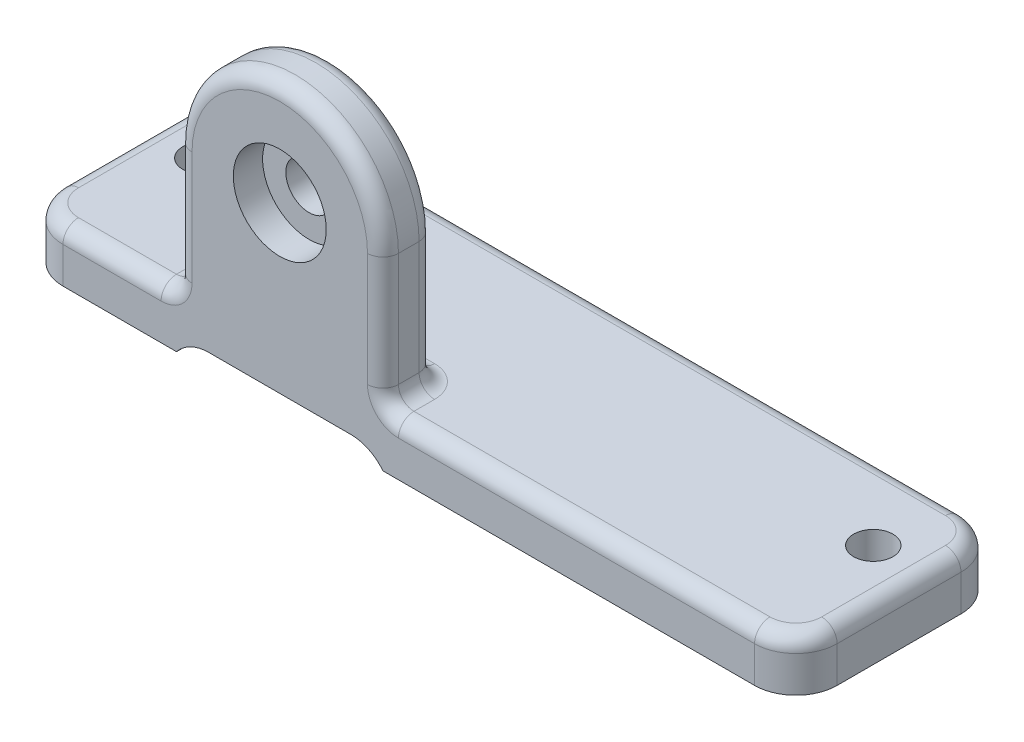
SolidWorks part; units mm, degrees
ref_plane "Front Plane" through (0, 0, 0) normal (0, 0, 1) x (1, 0, 0)
ref_plane "Top Plane" through (0, 0, 0) normal (0, 1, 0) x (1, 0, 0)
ref_plane "Right Plane" through (0, 0, 0) normal (1, 0, 0) x (0, 0, -1)
sketch "Croquis1" plane through (0, 0, 0) normal (0, 1, 0) x (1, 0, 0)
  line L1 (0, 0) -> (150, 0)
  line L2 (0, 0) -> (0, 40)
  line L3 (0, 40) -> (150, 40)
  line L4 (150, 0) -> (150, 40)
  dimension "D1" = 150
  dimension "D2" = 40
extrude "Saliente-Extruir1" add sketch "Croquis1" along normal blind 10 contours L2 L1 L4 L3
sketch "Croquis2" plane through (0, 0, 0) normal (0, 0, 1) x (1, 0, 0)
  line L0 (30, 0) -> (30, 35)
  line L1 (0, 0) -> (150, 0) construction
  line L2 (70, 35) -> (70, 0)
  line L3 (70, 0) -> (30, 0)
  line L4 (0, 10) -> (0, 0) construction
  arc A0 (30, 35) -> (70, 35) centre (50, 35) cw
  point P9 (0, 5)
  dimension "D3" = 20
  dimension "D1" = 50
  dimension "D2" = 35
extrude "Saliente-Extruir2" add sketch "Croquis2" against normal blind 10
sketch "Croquis3" plane through (0, 0, 0) normal (0, 0, 1) x (1, 0, 0)
  line L0 (0, 0) -> (150, 0) construction
  line L1 (30, 0) -> (70, 0)
  line L2 (30, 0) -> (30, 3)
  line L3 (30, 3) -> (70, 3)
  line L4 (70, 0) -> (70, 3)
  line L5 (30, 35) -> (30, 10) construction
  line L6 (70, 10) -> (70, 35) construction
  dimension "D1" = 3
extrude "Cortar-Extruir1" cut sketch "Croquis3" against normal through all
hole_wizard "Refrentado para perno con cabeza hexagonal de M81" positions "Croquis4" profile "Croquis5" counterbore size "M8" standard "Ansi Metric" end condition through all
sketch "Croquis4" plane through (0, 0, 0) normal (0, 0, 1) x (1, 0, 0)
  point P0 (50, 35)
sketch "Croquis5" plane through (50, 35, 0) normal (1, 0, 0) x (0, -1, 0)
  line L0 (0, 0) -> (0, 40)
  line L1 (0, 40) -> (4.5, 40)
  line L3 (4.5, 40) -> (4.5, 5.68)
  line L4 (4.5, 5.68) -> (9.005, 5.68)
  line L5 (9.005, 5.68) -> (9.005, 0)
  line L7 (9.005, 0) -> (0, 0)
  line L11 (0, -6.35) -> (0, 107.95) construction
  dimension "Diámetro de taladro hasta el siguiente" = 9
  dimension "Profundidad de taladro hasta el siguiente" = 40
  dimension "Diámetro de refrentado" = 18.01
  dimension "Profundidad de refrentado" = 5.68
fillet "Redondeo1" radius 8 2 edges at (70, 3, -20) (30, 3, -20)
fillet "Redondeo2" radius 8 4 edges at (150, 5, 0) (150, 5, -40) (0, 5, -40) (0, 5, 0)
fillet "Redondeo3" radius 3 18 edges at (30, 22.5, -10) (50, 55, -10) (30, 22.5, 0) (50, 55, 0) (70, 22.5, -10) (70, 22.5, 0) (2.3431, 10, -37.6569) (0, 10, -20) (75, 10, -40) (2.3431, 10, -2.3431) (147.6569, 10, -37.6569) (19, 10, 0) (150, 10, -20) (30, 10, -5) (147.6569, 10, -2.3431) (50, 10, -10) (106, 10, 0) (70, 10, -5)
hole_wizard "Taladro de margen para M71" positions "Croquis6" profile "Croquis7" hole size "M7" standard "Ansi Metric" end condition through all
sketch "Croquis6" plane through (0, 10, 0) normal (0, 1, 0) x (1, 0, 0)
  line L0 (8, 40) -> (142, 40) construction
  line L1 (0, 8) -> (0, 32) construction
  line L2 (150, 32) -> (150, 8) construction
  point P0 (140, 25)
  point P2 (10, 25)
  dimension "D1" = 15
  dimension "D2" = 10
  dimension "D3" = 15
  dimension "D4" = 10
sketch "Croquis7" plane through (140, 10, -25) normal (1, 0, 0) x (0, 0, 1)
  line L0 (0, 0) -> (0, 10)
  line L1 (0, 10) -> (3.8, 10)
  line L2 (3.8, 10) -> (3.8, 0)
  line L5 (3.8, 0) -> (0, 0)
  line L11 (0, -6.35) -> (0, 107.95) construction
  dimension "Diámetro de taladro hasta el siguiente" = 7.6
  dimension "Profundidad de taladro hasta el siguiente" = 10
